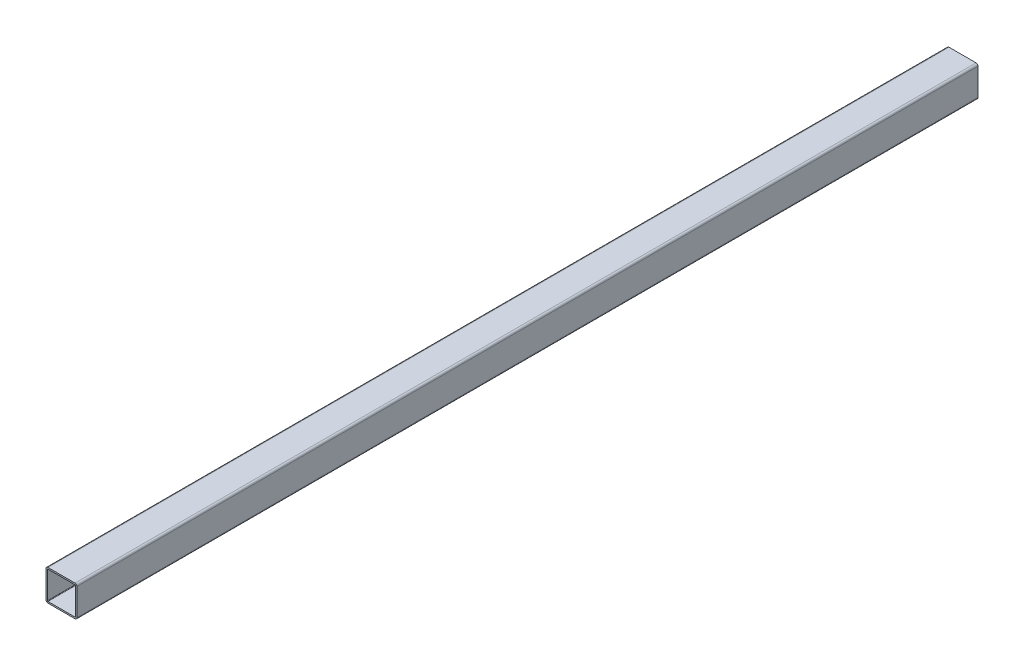
SolidWorks part; units mm, degrees
material "AISI 1010 Steel, hot rolled bar"
ref_plane "Front Plane" through (0, 0, 0) normal (0, 0, 1) x (1, 0, 0)
ref_plane "Top Plane" through (0, 0, 0) normal (0, 1, 0) x (1, 0, 0)
ref_plane "Right Plane" through (0, 0, 0) normal (1, 0, 0) x (0, 0, -1)
sketch "Sketch1" plane through (0, 0, 0) normal (0, 0, 1) x (1, 0, 0)
  line L0 (-14, 14.48) -> (14, 14.48)
  line L1 (-14, -16) -> (14, -16)
  line L2 (-16, -14) -> (-16, 14)
  line L3 (-14, 16) -> (14, 16)
  line L4 (16, -14) -> (16, 14)
  line L5 (-16, -16) -> (16, 16) construction
  line L6 (-16, 16) -> (16, -16) construction
  line L7 (14.48, -14) -> (14.48, 14)
  line L8 (-14, -14.48) -> (14, -14.48)
  line L9 (-14.48, -14) -> (-14.48, 14)
  arc A0 (14, -16) -> (16, -14) centre (14, -14) ccw
  arc A1 (-16, 14) -> (-14, 16) centre (-14, 14) cw
  arc A2 (-16, -14) -> (-14, -16) centre (-14, -14) ccw
  arc A3 (16, 14) -> (14, 16) centre (14, 14) ccw
  arc A4 (14.48, 14) -> (14, 14.48) centre (14, 14) ccw
  arc A5 (14, -14.48) -> (14.48, -14) centre (14, -14) ccw
  arc A6 (-14.48, -14) -> (-14, -14.48) centre (-14, -14) ccw
  arc A7 (-14.48, 14) -> (-14, 14.48) centre (-14, 14) cw
  point P0 (0, 0)
  dimension "D3" = 2
  dimension "D1" = 32
  dimension "D2" = 32
  dimension "D4" = 1.52
extrude "Boss-Extrude1" add sketch "Sketch1" along normal blind 466 and the other way blind 466
